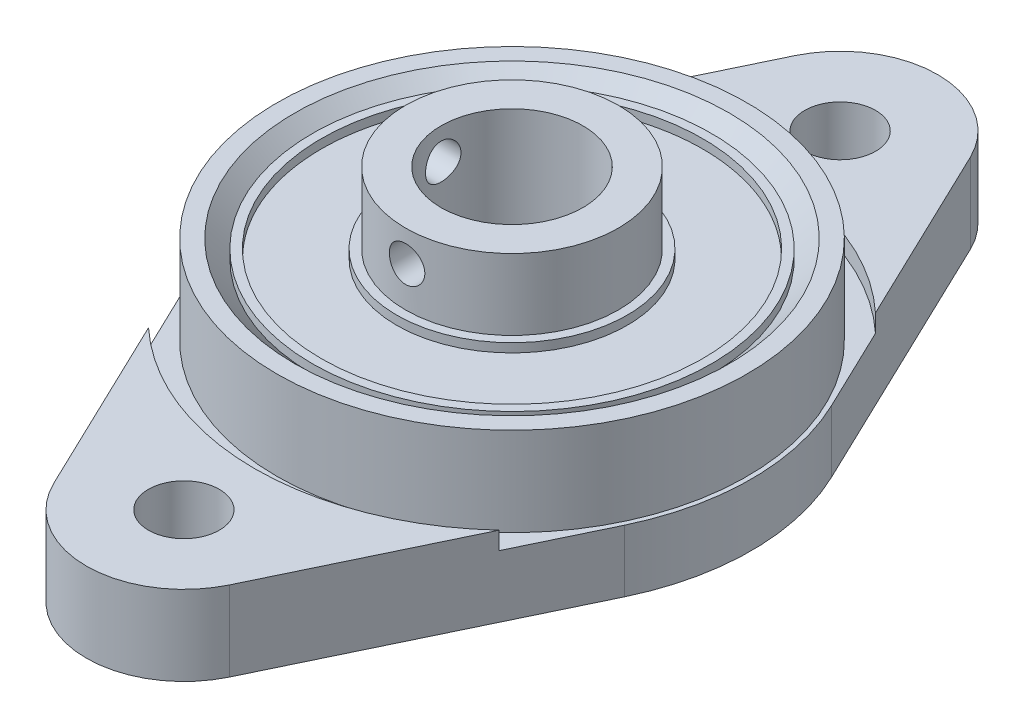
SolidWorks part; units mm, degrees
ref_plane "Front Plane" through (0, 0, 0) normal (0, 0, 1) x (1, 0, 0)
ref_plane "Top Plane" through (0, 0, 0) normal (0, 1, 0) x (1, 0, 0)
ref_plane "Right Plane" through (0, 0, 0) normal (1, 0, 0) x (0, 0, -1)
sketch "Sketch1" plane through (0, 0, 0) normal (0, 1, 0) x (1, 0, 0)
  line L0 (0, -18.5) -> (0, 18.5) construction
  line L1 (13.5, -24) -> (-13.5, -24) construction
  line L2 (13.5, -24) -> (13.5, 24) construction
  line L3 (13.5, 24) -> (-13.5, 24) construction
  line L4 (-13.5, -24) -> (-13.5, 24) construction
  line L5 (13.5, -24) -> (-13.5, 24) construction
  line L6 (13.5, 24) -> (-13.5, -24) construction
  line L7 (-14.85, 0) -> (14.85, 0) construction
  line L8 (12.1725, 5.8378) -> (4.9592, 20.8784)
  line L9 (0, -26.4) -> (0, 26.4) construction
  line L10 (-12.1725, 5.8378) -> (-4.9592, 20.8784)
  line L11 (-12.1725, -5.8378) -> (-4.9592, -20.8784)
  line L12 (12.1725, -5.8378) -> (4.9592, -20.8784)
  circle A0 centre (0, 0) radius 13.5
  circle A1 centre (0, 18.5) radius 2
  circle A2 centre (0, -18.5) radius 2
  circle A3 centre (0, 0) radius 4
  circle A4 centre (0, 0) radius 6
  circle A5 centre (0, 0) radius 13.25
  arc A6 (4.9592, 20.8784) -> (-4.9592, 20.8784) centre (0, 18.5) ccw
  arc A8 (4.9592, -20.8784) -> (-4.9592, -20.8784) centre (0, -18.5) cw
  arc A9 (-9.8843, -10.609) -> (9.8843, -10.609) centre (0, 0) ccw
  arc A10 (9.8843, 10.609) -> (-9.8843, 10.609) centre (0, 0) ccw
  circle A11 centre (0, 0) radius 14.5 construction
  circle A12 centre (0, 0) radius 12.25
  circle A13 centre (0, 0) radius 11.25
  point P0 (0, 0)
  point P11 (0, 0)
  point P32 (14, 0)
  dimension "D4" = 4
  dimension "D5" = 8
  dimension "D1" = 48
  dimension "D2" = 27
  dimension "D3" = 37
  dimension "D6" = 2
  dimension "D7" = 0.25
  dimension "D8" = 1
  dimension "D9" = 1.25
  dimension "D10" = 1
extrude "Boss-Extrude1" add sketch "Sketch1" along normal blind 4.5 contours A9 L11 A8 L12 A2 | A10 L8 A6 L10 A1 region at (0, 0, -14.7388) region at (7.2064, 0, 15.6404)
extrude "Boss-Extrude2" add sketch "Sketch1<3>" along normal blind 3.5 contours L11 A9 L12 A0 | L8 A10 L10 A0 | A0 A5 region at (0, 0, -13.7584) region at (13.1267, 0, -2.985) region at (10.7954, 0, 8.1117)
sketch "Sketch1<3>" plane through (0, 0, 0) normal (0, 1, 0) x (1, 0, 0) same geometry as "Sketch1"
extrude "Boss-Extrude3" add sketch "Sketch1<5>" along normal blind 8.5 contours A5 A12 region at (-12.8752, 0, 0)
sketch "Sketch1<5>" plane through (0, 0, 0) normal (0, 1, 0) x (1, 0, 0) same geometry as "Sketch1"
extrude "Boss-Extrude4" add sketch "Sketch1<6>" along normal blind 12 separate body contours A4 A3 region at (-5.8303, 0, 0)
sketch "Sketch1<6>" plane through (0, 0, 0) normal (0, 1, 0) x (1, 0, 0) same geometry as "Sketch1"
extrude "Boss-Extrude5" add sketch "Sketch1<7>" along normal blind 8.5 separate body contours A12 A13 region at (-11.9035, 0, 0)
sketch "Sketch1<7>" plane through (0, 0, 0) normal (0, 1, 0) x (1, 0, 0) same geometry as "Sketch1"
chamfer "Chamfer1" distance 1 angle 45 1 edges at (0, 8.5, 11.25)
ref_plane "Plane1" through (0, 4.25, 0) normal (0, -1, 0) x (-1, 0, 0)
sketch "Sketch2" plane through (0, 4.25, 0) normal (0, -1, 0) x (-1, 0, 0)
  line L0 (0, -18.5) -> (0, 18.5) construction
  circle A0 centre (0, 0) radius 11.25
  circle A1 centre (0, 0) radius 10.75
  circle A2 centre (0, 0) radius 6
  circle A3 centre (0, 0) radius 6.5
  dimension "D1" = 0.5
  dimension "D2" = 0.5
extrude "Boss-Extrude6" add sketch "Sketch2" along normal mid plane 7.5 contours A3 A2 | A0 A1 region at (10.9318, 4.25, 0) region at (6.3162, 4.25, 0)
extrude "Boss-Extrude7" add sketch "Sketch2<3>" along normal mid plane 6.5 separate body contours A1 A3 region at (10.4459, 4.25, 0)
sketch "Sketch2<3>" plane through (0, 4.25, 0) normal (0, -1, 0) x (-1, 0, 0) same geometry as "Sketch2"
sketch "Sketch3" plane through (0, 0, 0) normal (1, 0, 0) x (0, 0, -1)
  line L0 (13.25, 8.5) -> (-13.25, 8.5) construction
  line L1 (6, 12) -> (-6.0041, 12) construction
  line L2 (6, 12) -> (6, 8.5) construction
  line L3 (6, 8.5) -> (-6.0041, 8.5) construction
  line L4 (-6.0041, 12) -> (-6.0041, 8.5) construction
  line L5 (-0.002, 12) -> (-0.002, 8.5) construction
  circle A0 centre (-0.002, 10.25) radius 1
  circle A1 centre (-0.002, 10.25) radius 1.2
  dimension "D1" = 2
  dimension "D2" = 0.2
extrude "Cut-Extrude2" cut sketch "Sketch3" against normal blind 7.5 contours A0
pattern_circular "CirPattern1" count 2 every 90 about axis through (0, 12, 0) along (0, 1, 0) of "Cut-Extrude2"
sketch "Sketch4" [suppressed] plane through (0, 0, 0) normal (0, 1, 0) x (-1, 0, 0)
  line L0 (-11.0974, -5.753) -> (-5.376, -16.7896)
  line L1 (5.376, -16.7896) -> (11.0974, -5.753)
  line L2 (0, 6.6) -> (0, -6.6) construction
  line L4 (6.6, 0) -> (-6.6, 0) construction
  line L5 (5.376, 16.7896) -> (11.0974, 5.753)
  line L6 (-11.0974, 5.753) -> (-5.376, 16.7896)
  arc A0 (3.5879, -16.7647) -> (-3.5879, -16.7647) centre (0, -18.5) ccw
  arc A2 (11.0974, -5.753) -> (11.0974, 5.753) centre (0, 0) ccw
  arc A3 (-12.1725, 5.8378) -> (-12.1725, -5.8378) centre (0, 0) ccw construction
  arc A5 (3.5879, -16.7647) -> (5.376, -16.7896) centre (4.4882, -16.3293) ccw
  arc A6 (-3.5879, -16.7647) -> (-5.376, -16.7896) centre (-4.4882, -16.3293) cw
  arc A7 (3.5879, 16.7647) -> (5.376, 16.7896) centre (4.4882, 16.3293) cw
  arc A8 (3.5879, 16.7647) -> (-3.5879, 16.7647) centre (0, 18.5) cw
  arc A9 (-3.5879, 16.7647) -> (-5.376, 16.7896) centre (-4.4882, 16.3293) ccw
  arc A10 (-11.0974, 5.753) -> (-11.0974, -5.753) centre (0, 0) ccw
  dimension "D1" = 1
  dimension "D2" = 2
extrude "Cut-Extrude4" [suppressed] cut sketch "Sketch4" along normal up to surface (0.5 mm away)
